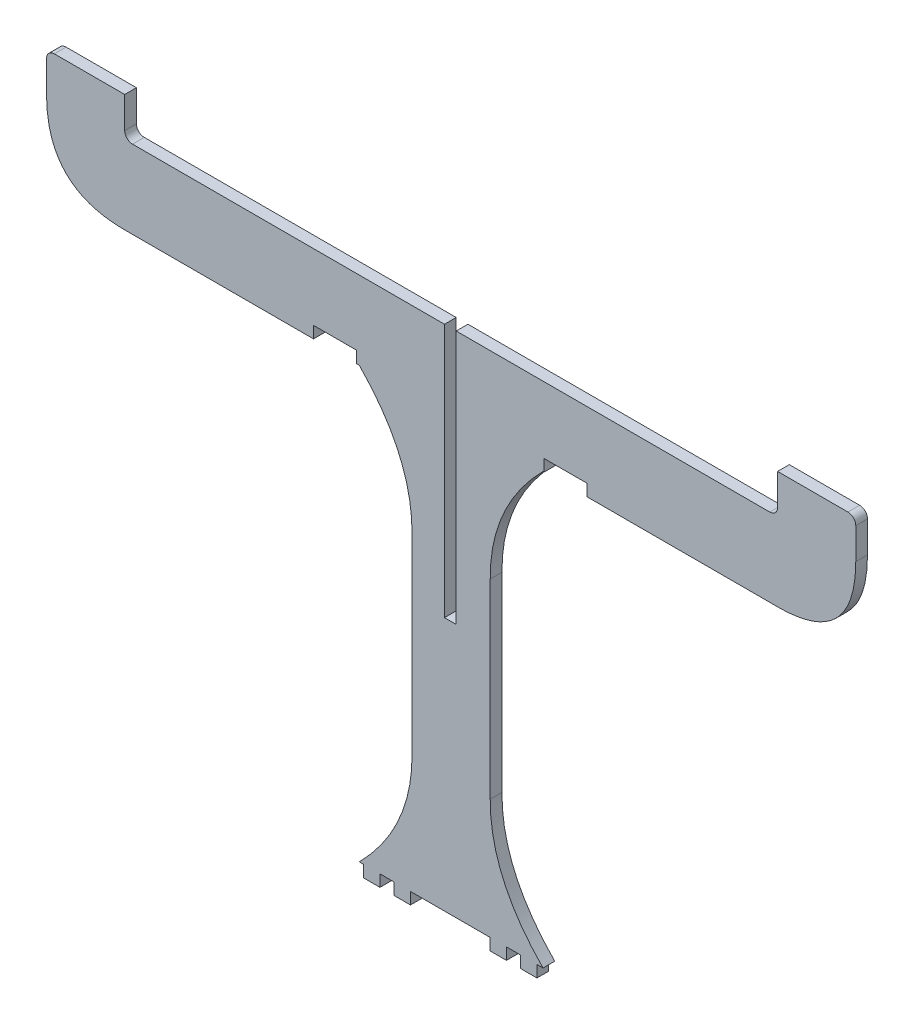
SolidWorks part; units mm, degrees
ref_plane "Přední rovina" through (0, 0, 0) normal (0, 0, 1) x (1, 0, 0)
ref_plane "Horní rovina" through (0, 0, 0) normal (0, 1, 0) x (1, 0, 0)
ref_plane "Pravá rovina" through (0, 0, 0) normal (1, 0, 0) x (0, 0, -1)
sketch "Skica1" plane through (0, 0, 0) normal (0, 0, 1) x (1, 0, 0)
  line L0 (-30.6426, 2.6943) -> (16.3574, 2.6943)
  line L1 (-7.1426, 2.6943) -> (-7.1426, -107.3057)
  line L2 (16.3574, -107.3057) -> (-30.6426, -107.3057)
  line L3 (-17.1426, 9.0001) -> (-17.1426, -176.0586) construction
  line L4 (27.2473, -27.3057) -> (-64.2445, -27.3057) construction
  line L5 (15.3668, -77.3057) -> (-64.2445, -77.3057) construction
  line L6 (-17.1426, -27.8784) -> (-17.1426, -76.656)
  line L7 (2.8574, -27.8784) -> (2.8574, -76.656)
  line L24 (-7.1426, -15.139) -> (-7.1426, 72.526) construction
  line L25 (10.652, -107.3057) -> (10.652, -110.3057)
  line L26 (10.652, -107.3057) -> (14.802, -107.3057)
  line L27 (14.802, -107.3057) -> (14.802, -110.3057)
  line L28 (10.652, -110.3057) -> (14.802, -110.3057)
  line L29 (2.852, -107.3057) -> (2.852, -110.3057)
  line L30 (2.852, -107.3057) -> (7.002, -107.3057)
  line L31 (7.002, -107.3057) -> (7.002, -110.3057)
  line L32 (2.852, -110.3057) -> (7.002, -110.3057)
  line L33 (-25.348, -110.3057) -> (-29.498, -110.3057)
  line L34 (-29.498, -107.3057) -> (-29.498, -110.3057)
  line L35 (-25.348, -107.3057) -> (-29.498, -107.3057)
  line L36 (-25.348, -107.3057) -> (-25.348, -110.3057)
  line L37 (-17.548, -110.3057) -> (-21.698, -110.3057)
  line L38 (-21.698, -107.3057) -> (-21.698, -110.3057)
  line L39 (-17.548, -107.3057) -> (-21.698, -107.3057)
  line L40 (-17.548, -107.3057) -> (-17.548, -110.3057)
  line L41 (-190.6426, 2.6943) -> (100.2644, 2.6943) construction
  line L42 (16.3574, 2.6943) -> (16.3574, 73.8241) construction
  line L43 (-30.6426, 73.8241) -> (-30.6426, 2.6943) construction
  line L44 (-110.6426, 2.6943) -> (-110.6426, 52.9232) construction
  line L45 (-190.6426, 32.6943) -> (86.9117, 32.6943) construction
  line L46 (-30.6426, 2.6943) -> (-90.6426, 2.6943)
  line L47 (-90.6426, -13.7924) -> (-90.6426, 96.8534) construction
  line L48 (-70.6426, -7.8313) -> (-70.6426, 84.4343) construction
  line L49 (-194.5635, 22.6943) -> (-7.1426, 22.6943) construction
  line L50 (-108.6426, 32.6943) -> (-90.6426, 32.6943)
  line L51 (-90.6426, 32.6943) -> (-90.6426, 24.6943)
  line L52 (-110.6426, 22.6943) -> (-110.6426, 30.6943)
  line L53 (16.3574, 2.6943) -> (76.3574, 2.6943)
  line L54 (-110.6426, 22.6943) -> (-110.6426, 2.6943) construction
  line L55 (76.3574, 32.6943) -> (76.3574, 24.6943)
  line L56 (-110.6426, 2.6943) -> (-90.6426, 2.6943) construction
  line L57 (94.3574, 32.6943) -> (76.3574, 32.6943)
  line L58 (-88.6426, 22.6943) -> (74.3574, 22.6943)
  line L59 (-7.1426, 22.6943) -> (-7.1426, 2.6943)
  line L60 (96.3574, 22.6943) -> (96.3574, 30.6943)
  line L61 (96.3574, 22.6943) -> (96.3574, 2.6943) construction
  line L62 (96.3574, 2.6943) -> (76.3574, 2.6943) construction
  arc A0 (74.3574, 22.6943) -> (76.3574, 24.6943) centre (74.3574, 24.6943) ccw
  arc A1 (-88.6426, 22.6943) -> (-90.6426, 24.6943) centre (-88.6426, 24.6943) cw
  arc A2 (-110.6426, 30.6943) -> (-108.6426, 32.6943) centre (-108.6426, 30.6943) cw
  arc A3 (96.3574, 30.6943) -> (94.3574, 32.6943) centre (94.3574, 30.6943) ccw
  spline S0 degree 2 poles (-30.6426, 2.6943) (-17.0251, -11.1181) (-17.1426, -27.8784) knots 0 0 0 1 1 1
  spline S1 degree 2 poles (-30.6426, -107.3057) (-17.0093, -93.4583) (-17.1426, -76.656) knots 0 0 0 1 1 1
  spline S2 degree 2 poles (16.3574, 2.6943) (2.7399, -11.1181) (2.8574, -27.8784) knots 0 0 0 1 1 1
  spline S3 degree 2 poles (16.3574, -107.3057) (2.724, -93.4583) (2.8574, -76.656) knots 0 0 0 1 1 1
  spline S4 degree 2 poles (-110.6426, 22.6943) (-110.6426, 2.6943) (-90.6426, 2.6943) knots 0 0 0 1 1 1
  spline S5 degree 2 poles (96.3574, 22.6943) (96.3574, 2.6943) (76.3574, 2.6943) knots 0 0 0 1 1 1
  point P37 (-110.6426, 22.6943)
  point P54 (-110.6426, 32.6943)
  point P55 (-90.6426, 32.6943)
  point P56 (-90.6426, 22.6943)
  point P70 (-90.6426, 22.6943)
  point P73 (-110.6426, 32.6943)
  dimension "D15" = 60
  dimension "D17" = 2
  dimension "D18" = 2
  dimension "D1" = 110
  dimension "D2" = 23.5
  dimension "D3" = 30
  dimension "D4" = 30
  dimension "D5" = 30.6498
  dimension "D6" = 23.5
  dimension "D7" = 47
  dimension "D8" = 30
  dimension "D9" = 30
  dimension "D10" = 20
  dimension "D11" = 80
  dimension "D12" = 20
  dimension "D13" = 40
  dimension "D14" = 10
extrude "Přidat vysunutím2" add sketch "Skica1" along normal blind 3 contours S1 L2 L1 L0 S0 L6 | L2 S3 L7 S2 L0 L1 | L0 | L0 | L0 | L0 | L40 L2 L38 L37 | L36 L2 L34 L33 | L29 L32 L31 L2 | L25 L28 L27 L2 region at (-61.2298, 14.2338, 0) region at (-13.8581, -52.3107, 0) region at (46.9445, 14.2338, 0) region at (-0.4272, -52.3107, 0) region at (4.927, -108.8057, 0) region at (-19.623, -108.8057, 0) region at (-27.423, -108.8057, 0) region at (12.727, -108.8057, 0)
sketch "Skica2" plane through (0, 0, 0) normal (0, 0, -1) x (-1, 0, 0)
  line L0 (7.348, -129.2799) -> (7.348, 48.5683) construction
  line L1 (50.2587, -42.3057) -> (-73.7805, -42.3057) construction
  line L2 (-2.852, -107.3057) -> (17.548, -107.3057) construction
  line L5 (8.848, -107.3057) -> (5.848, -107.3057)
  line L8 (8.848, 22.6943) -> (5.848, 22.6943)
  line L9 (8.848, 22.6943) -> (8.848, -42.3057)
  line L10 (8.848, -42.3057) -> (5.848, -42.3057)
  line L11 (5.848, 22.6943) -> (5.848, -42.3057)
  line L12 (8.848, 22.6943) -> (5.848, -42.3057) construction
  line L13 (8.848, -42.3057) -> (5.848, 22.6943) construction
  point P5 (7.348, -84.8057)
  point P8 (7.348, -9.8057)
  dimension "D1" = 65
  dimension "D2" = 130
  dimension "D4" = 3
  dimension "D5" = 3
extrude "Odebrat vysunutím3" cut sketch "Skica2" against normal blind 3 contours L11 L10 L9 L8
sketch "Skica3" plane through (0, 0, 0) normal (0, 0, -1) x (-1, 0, 0)
  line L0 (55.2295, 0) -> (-43.3821, 0) construction
  line L1 (7.348, -107.3057) -> (7.348, 33.6673) construction
  line L2 (-16.652, 0) -> (-27.652, 0)
  line L3 (-16.652, 0) -> (-16.652, 5.6943)
  line L4 (-16.652, 5.6943) -> (-27.652, 5.6943)
  line L5 (-27.652, 0) -> (-27.652, 5.6943)
  line L6 (-2.852, -107.3057) -> (17.548, -107.3057) construction
  line L7 (-16.3574, 2.6943) -> (-76.3574, 2.6943) construction
  line L8 (31.348, 5.6943) -> (42.348, 5.6943)
  line L9 (42.348, 0) -> (42.348, 5.6943)
  line L10 (31.348, 0) -> (42.348, 0)
  line L11 (31.348, 0) -> (31.348, 5.6943)
  point P11 (7.348, 0)
  dimension "D1" = 24
  dimension "D2" = 35
  dimension "D3" = 3
extrude "Odebrat vysunutím4" cut sketch "Skica3" against normal blind 3
